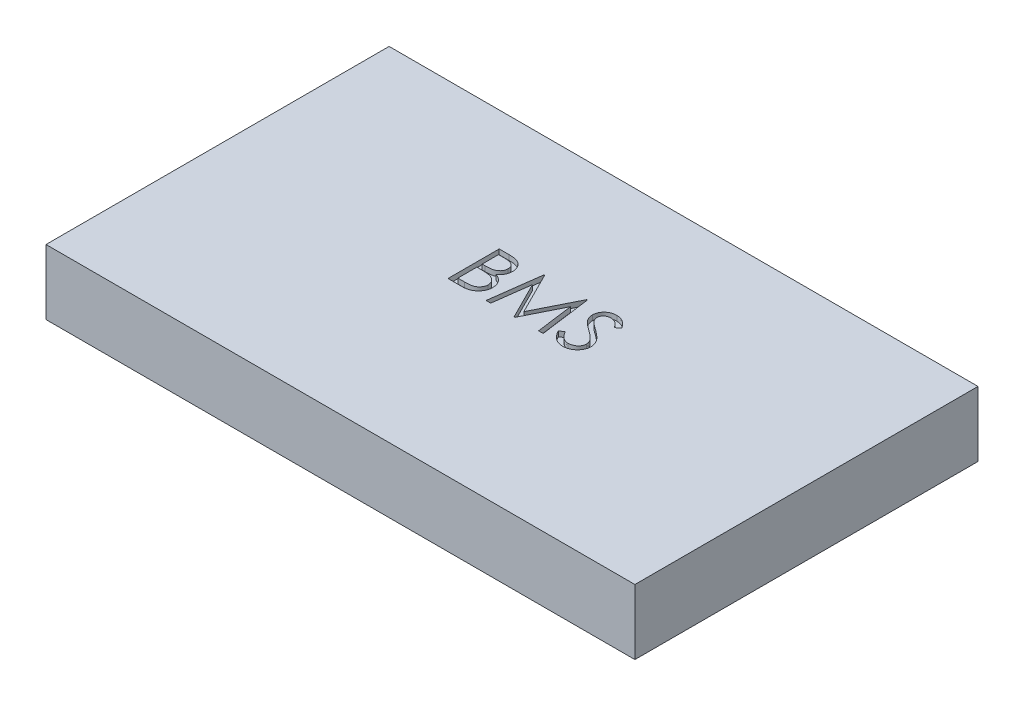
SolidWorks part; units mm, degrees
ref_plane "Front Plane" through (0, 0, 0) normal (0, 0, 1) x (1, 0, 0)
ref_plane "Top Plane" through (0, 0, 0) normal (0, 1, 0) x (1, 0, 0)
ref_plane "Right Plane" through (0, 0, 0) normal (1, 0, 0) x (0, 0, -1)
sketch "Sketch1" plane through (0, 0, 0) normal (0, 1, 0) x (1, 0, 0)
  line L1 (0, 0) -> (115, 0)
  line L2 (0, 0) -> (0, 67)
  line L3 (0, 67) -> (115, 67)
  line L4 (115, 0) -> (115, 67)
  dimension "D1" = 67
  dimension "D2" = 115
extrude "Boss-Extrude1" add sketch "Sketch1" along normal blind 12.7
sketch "Sketch2" plane through (0, 12.7, 0) normal (0, 1, 0) x (1, 0, 0)
  line L0 (0, 33.5) -> (115, 33.5) construction
  line L1 (0, 67) -> (0, 0) construction
  line L2 (115, 0) -> (115, 67) construction
  text T0 "BMS" font "Century Gothic" height 10
extrude "Cut-Extrude1" cut sketch "Sketch2" against normal blind 1
